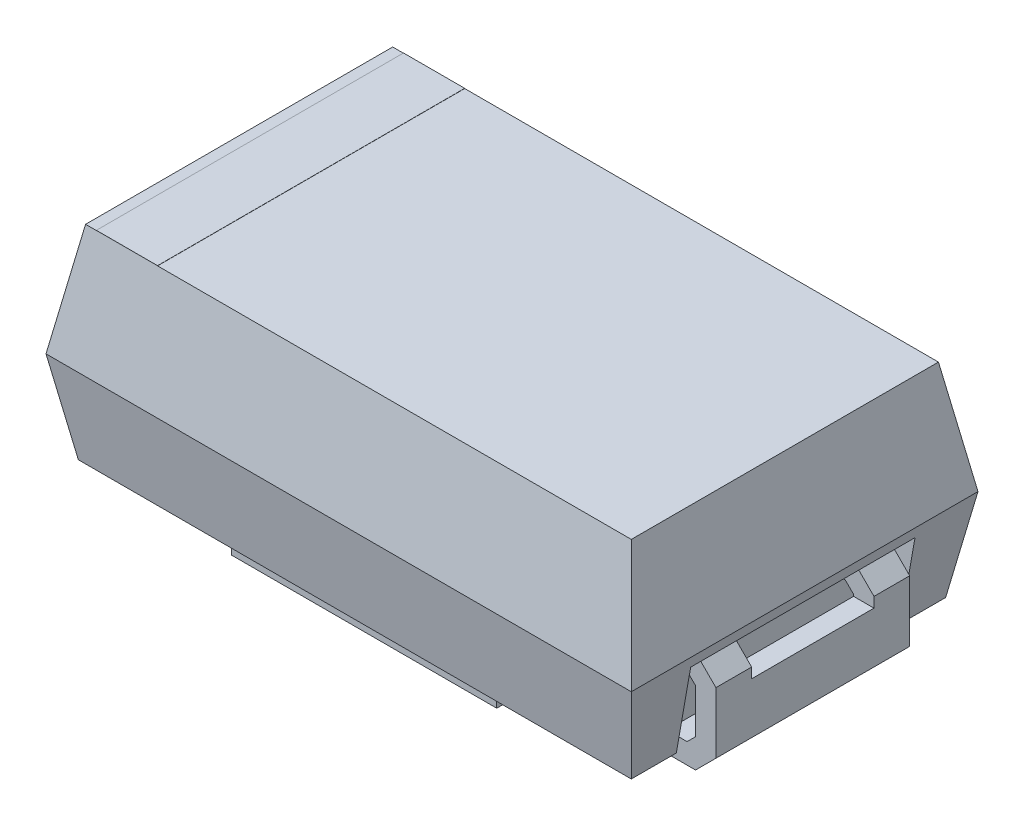
SolidWorks part; units mm, degrees
ref_plane "Front Plane" through (0, 0, 0) normal (0, 0, 1) x (1, 0, 0)
ref_plane "Top Plane" through (0, 0, 0) normal (0, 1, 0) x (1, 0, 0)
ref_plane "Right Plane" through (0, 0, 0) normal (1, 0, 0) x (0, 0, -1)
ref_plane "Plane5" through (-0.1524, 0, 0) normal (1, 0, 0) x (0, 0, -1)
sketch "Sketch2" plane through (-0.1524, 0, 0) normal (1, 0, 0) x (0, 0, -1)
  line L1 (2.159, 2.794) -> (-2.159, 2.794)
  line L2 (2.159, 2.794) -> (2.159, 0)
  line L3 (2.159, 0) -> (-2.159, 0)
  line L4 (-2.159, 2.794) -> (-2.159, 0)
  dimension "D1" = 2.794
  dimension "D2" = 4.318
extrude "Base-Extrude" add sketch "Sketch2" along normal blind 7.2898
chamfer "Chamfer1" distance 1.397 angle 10 4 edges at (7.1374, 0, 0) (-0.1524, 0, 0) (3.4925, 0, -2.159) (3.4925, 0, 2.159)
sketch "Sketch3" plane through (-0.1524, 0, 0) normal (-1, 0, 0) x (0, 0, 1)
  line L0 (1.9127, 0) -> (-1.9127, 0) construction
  line L1 (-1.397, 1.27) -> (1.397, 1.27)
  line L2 (-1.397, 1.27) -> (-1.397, 0)
  line L3 (-1.397, 0) -> (1.397, 0)
  line L4 (1.397, 1.27) -> (1.397, 0)
  dimension "D1" = 1.27
  dimension "D2" = 1.397
  dimension "D3" = 2.794
extrude "Cut-Extrude1" cut sketch "Sketch3" against normal blind 0.508
sketch "Sketch4" plane through (7.1374, 0, 0) normal (1, 0, 0) x (0, 0, -1)
  line L0 (-1.397, 0) -> (1.397, 0)
  line L1 (1.9127, 0) -> (-1.9127, 0) construction
  line L2 (-1.397, 1.27) -> (1.397, 1.27)
  line L3 (1.397, 0) -> (1.397, 1.27)
  line L4 (-1.397, 0) -> (-1.397, 1.27)
  dimension "D1" = 2.794
  dimension "D2" = 1.397
  dimension "D3" = 1.27
extrude "Cut-Extrude2" cut sketch "Sketch4" against normal blind 0.508
sketch "Sketch5" plane through (0, 0, 0) normal (0, -1, 0) x (1, 0, 0)
  line L1 (5.08, -1.778) -> (1.778, -1.778)
  line L2 (5.08, -1.778) -> (5.08, 1.778)
  line L3 (5.08, 1.778) -> (1.778, 1.778)
  line L4 (1.778, -1.778) -> (1.778, 1.778)
  dimension "D1" = 3.556
  dimension "D2" = 1.778
  dimension "D3" = 1.778
  dimension "D4" = 3.302
extrude "Cut-Extrude3" cut sketch "Sketch5" against normal blind 0.254 flip side to cut
chamfer "Chamfer2" distance 1.397 angle 10 8 edges at (7.1374, 2.0955, 2.159) (-0.1524, 2.0955, -2.159) (7.1374, 2.0955, -2.159) (-0.1524, 2.0955, 2.159) (-0.1524, 2.794, 0) (7.1374, 2.794, 0) (3.4925, 2.794, 2.159) (3.4925, 2.794, -2.159)
sketch "Sketch6" plane through (0, 0, 0) normal (0, 0, 1) x (1, 0, 0)
  line L0 (0, 0) -> (1.2954, 0)
  line L1 (-0.254, 0.254) -> (-0.254, 1.016)
  line L2 (0, 0) -> (-0.254, 0.254)
  line L3 (-0.254, 1.016) -> (-0.0026, 1.2674)
  line L4 (-0.0026, 1.2674) -> (0.2955, 1.2674)
  dimension "D1" = 1.2954
  dimension "D2" = 135
  dimension "D3" = 0.254
  dimension "D4" = 0.762
  dimension "D5" = 135
  dimension "D6" = 0.3556
extrude "Boss-Extrude-Thin1" add sketch "Sketch6" along normal mid plane 2.413 thin thin type one direction wall 0.254
sketch "Sketch7" plane through (-0.254, 0, 0) normal (-1, 0, 0) x (0, 0, 1)
  line L0 (1.397, 1.27) -> (-1.397, 1.27) construction
  line L1 (-0.762, 0.889) -> (0.762, 0.889)
  line L2 (-0.762, 0.889) -> (-0.762, 1.27)
  line L3 (-0.762, 1.27) -> (0.762, 1.27)
  line L4 (0.762, 0.889) -> (0.762, 1.27)
  dimension "D1" = 0.381
  dimension "D2" = 0.762
  dimension "D3" = 1.524
extrude "Cut-Extrude4" cut sketch "Sketch7" against normal blind 0.508
ref_plane "Plane6" through (3.4925, 0, 0) normal (1, 0, 0) x (0, 0, -1)
mirror "Mirror1" about plane through (3.4925, 0, 0) normal (1, 0, 0) of "Cut-Extrude4", "Boss-Extrude-Thin1"
sketch "Sketch8" plane through (0, 2.794, 0) normal (0, 1, 0) x (-1, 0, 0)
  line L0 (-6.8911, -1.9127) -> (-0.0939, -1.9127) construction
  line L1 (-0.2286, -1.9127) -> (-0.9906, -1.9127)
  line L2 (-0.2286, -1.9127) -> (-0.2286, 1.9127)
  line L3 (-0.2286, 1.9127) -> (-0.9906, 1.9127)
  line L4 (-0.9906, -1.9127) -> (-0.9906, 1.9127)
  line L5 (-0.0939, 1.9127) -> (-6.8911, 1.9127) construction
  dimension "D1" = 0.9906
  dimension "D2" = 0.762
extrude "Boss-Extrude2" add sketch "Sketch8" along normal blind 0.0025
sketch "Component_Outline" plane through (0, 0, 0) normal (0, 1, 0) x (1, 0, 0)
  line L0 (-0.1524, -2.159) -> (7.1374, -2.159)
  line L1 (7.1374, -2.159) -> (7.1374, -1.2065)
  line L2 (6.985, -1.2065) -> (7.239, -1.2065) construction
  line L3 (7.1374, -2.159) -> (7.1374, 2.159) construction
  line L4 (7.1374, -1.2065) -> (7.239, -1.2065)
  line L5 (7.239, -1.2065) -> (7.239, 1.2065)
  line L6 (7.239, 1.2065) -> (7.1374, 1.2065)
  line L7 (6.985, 1.2065) -> (7.239, 1.2065) construction
  line L8 (7.1374, 1.2065) -> (7.1374, 2.159)
  line L9 (7.1374, 2.159) -> (-0.1524, 2.159)
  line L10 (-0.1524, 2.159) -> (-0.1524, 1.2065)
  line L11 (0, 1.2065) -> (-0.254, 1.2065) construction
  line L12 (-0.1524, 2.159) -> (-0.1524, -2.159) construction
  line L13 (-0.1524, 1.2065) -> (-0.254, 1.2065)
  line L14 (-0.254, 1.2065) -> (-0.254, -1.2065)
  line L15 (-0.254, -1.2065) -> (-0.1524, -1.2065)
  line L16 (0, -1.2065) -> (-0.254, -1.2065) construction
  line L17 (-0.1524, -1.2065) -> (-0.1524, -2.159)
